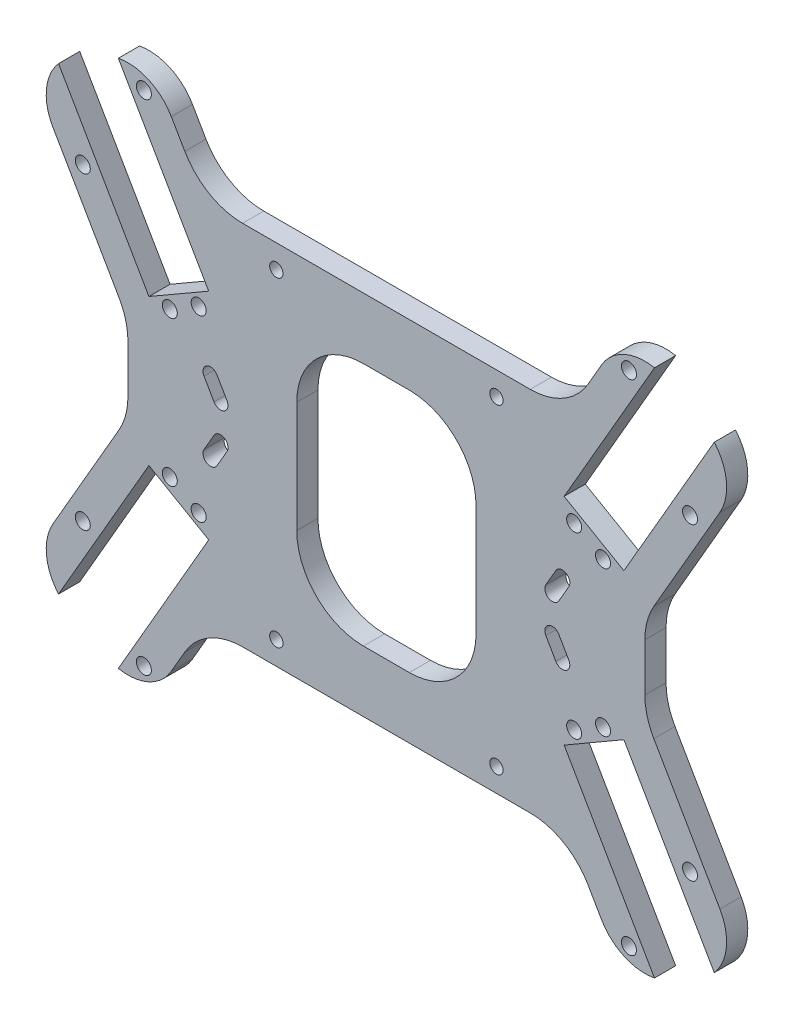
SolidWorks part; units mm, degrees
material "Erable"
ref_plane "Plan de face" through (0, 0, 0) normal (0, 0, 1) x (1, 0, 0)
ref_plane "Plan de dessus" through (0, 0, 0) normal (0, 1, 0) x (1, 0, 0)
ref_plane "Plan de droite" through (0, 0, 0) normal (1, 0, 0) x (0, 0, -1)
sketch "Esquisse3" plane through (0, 0, 0) normal (0, 0, 1) x (1, 0, 0)
  line L0 (0, -3.4925) -> (0, 3.4925) construction
  line L1 (-54.6725, 55) -> (54.6725, 55)
  line L2 (-77.5, 12.5385) -> (-77.5, -12.5385)
  line L3 (-54.6725, -55) -> (54.6725, -55)
  line L4 (77.5, 12.5385) -> (77.5, -12.5385)
  line L5 (3.4925, 0) -> (-3.4925, 0) construction
  line L6 (-54.6725, 55) -> (-71.993, 85)
  line L7 (-71.993, 85) -> (-107.5, 64.5)
  line L8 (-107.5, 64.5) -> (-77.5, 12.5385)
  line L9 (-77.5, -12.5385) -> (-107.5, -64.5)
  line L10 (-107.5, -64.5) -> (-71.993, -85)
  line L11 (-71.993, -85) -> (-54.6725, -55)
  line L12 (54.6725, 55) -> (71.993, 85)
  line L13 (71.993, 85) -> (107.5, 64.5)
  line L14 (107.5, 64.5) -> (77.5, 12.5385)
  line L15 (77.5, -12.5385) -> (107.5, -64.5)
  line L16 (107.5, -64.5) -> (71.993, -85)
  line L17 (71.993, -85) -> (54.6725, -55)
  line L19 (-26.875, 36.6667) -> (26.875, 36.6667)
  line L20 (-26.875, 36.6667) -> (-26.875, -36.6667)
  line L21 (-26.875, -36.6667) -> (26.875, -36.6667)
  line L22 (26.875, 36.6667) -> (26.875, -36.6667)
  point P4 (0, 55)
  point P7 (-77.5, 0)
  point P24 (0, -36.6667)
  point P27 (26.875, 0)
  dimension "D3" = 120
  dimension "D6" = 41
  dimension "D7" = 120
  dimension "D8" = 120
  dimension "D9" = 120
  dimension "D2" = 110
  dimension "D10" = 53.75
  dimension "D11" = 73.3333
  dimension "D4" = 170
  dimension "D5" = 215
  dimension "D12" = 60
extrude "Boss.-Extru.2" add sketch "Esquisse3" against normal blind 6.35 separate body
fillet "Congé6" radius 20 12 edges at (77.5, -12.5385, -3.175) (77.5, 12.5385, -3.175) (54.6725, 55, -3.175) (-54.6725, 55, -3.175) (-77.5, 12.5385, -3.175) (-77.5, -12.5385, -3.175) (-54.6725, -55, -3.175) (54.6725, -55, -3.175) (26.875, -36.6667, -3.175) (26.875, 36.6667, -3.175) (-26.875, -36.6667, -3.175) (-26.875, 36.6667, -3.175)
fillet "Congé7" radius 15 8 edges at (71.993, -85, -3.175) (107.5, -64.5, -3.175) (107.5, 64.5, -3.175) (71.993, 85, -3.175) (-71.993, 85, -3.175) (-107.5, 64.5, -3.175) (-71.993, -85, -3.175) (-107.5, -64.5, -3.175)
sketch "Esquisse4" plane through (0, 0, 0) normal (0, 0, 1) x (1, 0, 0)
  line L0 (-53.2831, 32.2936) -> (-74.2831, 68.6667)
  line L1 (-74.2831, 68.6667) -> (-92.2098, 58.3167) construction
  line L2 (-92.2098, 58.3167) -> (-71.2098, 21.9436)
  line L3 (-71.2098, 21.9436) -> (-53.2831, 32.2936)
  line L4 (-83.2465, 63.4917) -> (-89.7465, 74.75) construction
  line L5 (-84.9833, 77.5) -> (-94.5096, 72) construction
  line L6 (-60.446, 65) -> (-64.493, 72.0096) construction
  line L7 (-49.7465, 5.468) -> (-52.7465, 10.6641) construction
  line L8 (-51.695, 4.343) -> (-54.695, 9.5391)
  line L9 (-47.7979, 6.593) -> (-50.7979, 11.7891)
  line L10 (-56.2914, 26.804) -> (-80.5414, 68.8063) construction
  line L11 (-80.5414, 68.8063) -> (-89.2016, 63.8063) construction
  line L12 (-89.2016, 63.8063) -> (-64.9516, 21.804) construction
  line L13 (-64.9516, 21.804) -> (-56.2914, 26.804) construction
  line L14 (-81.7098, 40.1301) -> (-77.0766, 42.8051) construction
  line L15 (-92.2098, 58.3167) -> (-98.7098, 69.575)
  line L16 (-98.7098, 69.575) -> (-80.7831, 79.925)
  line L17 (-80.7831, 79.925) -> (-74.2831, 68.6667)
  line L18 (-84.9833, 77.5) -> (-94.5096, 72) construction
  arc A0 (-51.695, 4.343) -> (-47.7979, 6.593) centre (-49.7465, 5.468) ccw
  arc A1 (-50.7979, 11.7891) -> (-54.695, 9.5391) centre (-52.7465, 10.6641) ccw
  circle A2 centre (-91.04, 46.2904) radius 2.25
  circle A3 centre (-56.2914, 26.804) radius 2.25
  circle A4 centre (-64.9516, 21.804) radius 2.25
  circle A7 centre (-72.7226, 74.7638) radius 2.25
  point P12 (-51.2465, 8.066)
  point P23 (-84.8715, 66.3063)
  dimension "D5" = 2.25
  dimension "D7" = 48.5
  dimension "D9" = 4.5
  dimension "D10" = 5
  dimension "D1" = 20.7
  dimension "D2" = 42
  dimension "D3" = 13
  dimension "D4" = 19
  dimension "D6" = 6
  dimension "D8" = 10
  dimension "D11" = 4.5
  dimension "D12" = 4.4
  dimension "D13" = 11
extrude "Enlèv. mat.-Extru.2" cut sketch "Esquisse4" against normal blind 6.35
mirror "Symétrie1" about plane through (0, 0, 0) normal (0, 1, 0) of "Enlèv. mat.-Extru.2"
mirror "Symétrie2" about plane through (0, 0, 0) normal (1, 0, 0) of "Symétrie1"
sketch "Esquisse5" plane through (0, 0, 0) normal (0, 0, 1) x (1, 0, 0)
  line L0 (0, -3.4925) -> (0, 3.4925) construction
  line L1 (-33, 48) -> (33, 48) construction
  line L2 (-33, 48) -> (-33, -48) construction
  line L3 (-33, -48) -> (33, -48) construction
  line L4 (33, 48) -> (33, -48) construction
  line L5 (3.4925, 0) -> (-3.4925, 0) construction
  point P6 (0, 48)
  point P7 (-33, 0)
  dimension "D1" = 66
  dimension "D2" = 96
hole_wizard "Diamètre du perçage Ø4.0 (4)1" positions "Esquisse6" profile "Esquisse7" hole size "Ø4.0" standard "Ansi Metric" end condition through all
sketch "Esquisse6" plane through (0, 0, 0) normal (0, 0, 1) x (1, 0, 0)
  point P0 (33, 48)
  point P3 (-33, 48)
  point P6 (-33, -48)
  point P9 (33, -48)
sketch "Esquisse7" plane through (33, 48, 0) normal (1, 0, 0) x (0, -1, 0)
  line L0 (0, 0) -> (0, 6.35)
  line L1 (0, 6.35) -> (2, 6.35)
  line L2 (2, 6.35) -> (2, 0)
  line L5 (2, 0) -> (0, 0)
  line L11 (0, -6.35) -> (0, 107.95) construction
  dimension "Diamètre du perçage jusqu'au prochain" = 4
  dimension "Profondeur du perçage jusqu'au prochain" = 6.35
sketch "Esquisse8" plane through (0, 0, 0) normal (0, 0, 1) x (1, 0, 0)
  line L1 (-102.0096, 79.5096) -> (102.0096, 79.5096) construction
  line L2 (-102.0096, 79.5096) -> (-102.0096, -79.5096) construction
  line L3 (-102.0096, -79.5096) -> (102.0096, -79.5096) construction
  line L4 (102.0096, 79.5096) -> (102.0096, -79.5096) construction
  arc A0 (98.307, -68.8772) -> (100, -51.5096) centre (87.0096, -59.0096) ccw construction
  arc A1 (64.493, -72.0096) -> (80.3803, -79.2272) centre (77.4833, -64.5096) ccw construction
  arc A2 (-64.493, 72.0096) -> (-80.3803, 79.2272) centre (-77.4833, 64.5096) ccw construction
  arc A3 (-98.307, 68.8772) -> (-100, 51.5096) centre (-87.0096, 59.0096) ccw construction
  dimension "D1" = 204.0192
  dimension "D2" = 159.0192
equation "\"D10@Esquisse3\"=\"D5@Esquisse3\"/4"
equation "\"D11@Esquisse3\"=\"D2@Esquisse3\"/1.5"
